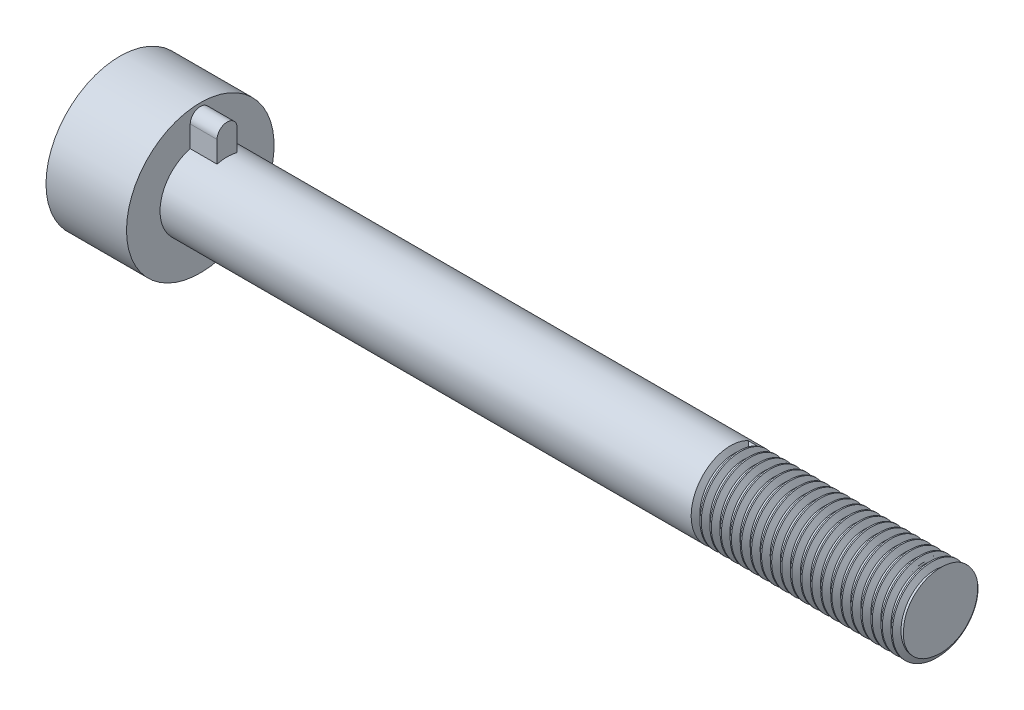
SolidWorks part; units mm, degrees
ref_plane "Front Plane" through (0, 0, 0) normal (0, 0, 1) x (1, 0, 0)
ref_plane "Top Plane" through (0, 0, 0) normal (0, 1, 0) x (1, 0, 0)
ref_plane "Right Plane" through (0, 0, 0) normal (1, 0, 0) x (0, 0, -1)
sketch "Sketch1" plane through (0, 0, 0) normal (0, 1, 0) x (1, 0, 0)
  line L0 (0, 0) -> (122, 0) construction
  line L1 (0, 0) -> (0, 11)
  line L2 (0, 11) -> (12, 11)
  line L3 (12, 11) -> (12, 6)
  line L4 (12, 6) -> (122, 6)
  line L5 (122, 6) -> (122, 0)
  line L6 (0, 0) -> (122, 0)
  dimension "D1" = 122
  dimension "D2" = 22
  dimension "D3" = 12
  dimension "D4" = 12
revolve "Revolve1" add sketch "Sketch1" angle 360 about L0
thread "Thread1" pitch 1.5 method cut trim with start face yes profile "Thread Profile1" start angle 0, offset 2, length 32, pitch 1.5, diameter 12
ref_plane "Plane1" through (124, 0, 6) normal (0, -1, 0) x (0, 0, 1)
sketch "Thread Profile1" plane through (124, 0, 6) normal (0, -1, 0) x (0, 0, 1)
  line L0 (0, 0) -> (0, 1.5) construction
  line L11 (0, 0) -> (0, 1.3125)
  line L12 (0, 1.3125) -> (-0.8119, 0.8437)
  line L13 (-0.8119, 0.8437) -> (-0.8119, 0.4687)
  line L15 (-0.8119, 0.4687) -> (0, 0)
  line L17 (-0.8119, 0.6562) -> (0, 0.6562) construction
  point P2 (0, 0)
  dimension "Pitch" = 1.5
  dimension "Profile_Angle" = 60
  dimension "Profile_Land" = 0.375
  dimension "Profile_Height" = 0.8119
sketch "Sketch4" plane through (12, 0, 0) normal (1, 0, 0) x (0, 0, -1)
  line L0 (-1.5, 9) -> (-1.5, 5.8095)
  line L1 (1.5, 9) -> (1.5, 5.8095)
  arc A0 (1.5, 9) -> (-1.5, 9) centre (0, 9) ccw
  circle A1 centre (0, 0) radius 6 construction
  arc A2 (1.5, 5.8095) -> (-1.5, 5.8095) centre (0, 0) ccw
  point P10 (0, 0)
  point P11 (0, 0)
  dimension "D1" = 3
  dimension "D2" = 9
extrude "Boss-Extrude1" add sketch "Sketch4" along normal blind 4
